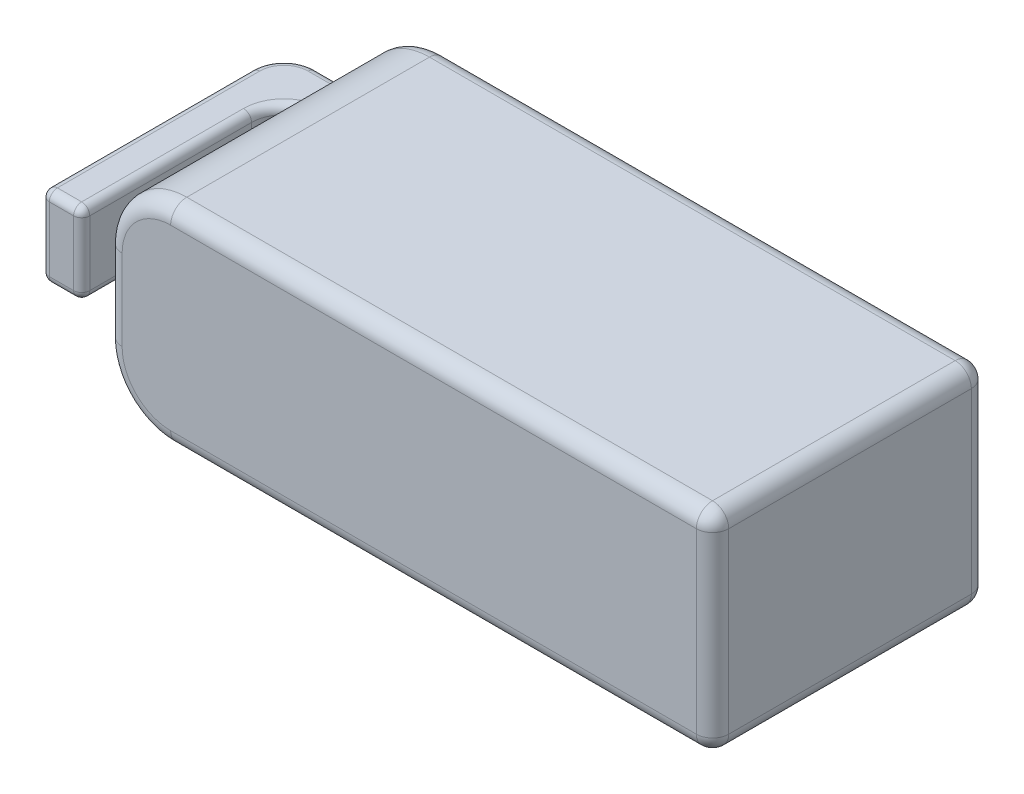
SolidWorks part; units mm, degrees
ref_plane "Plan de face" through (0, 0, 0) normal (0, 0, 1) x (1, 0, 0)
ref_plane "Plan de dessus" through (0, 0, 0) normal (0, 1, 0) x (1, 0, 0)
ref_plane "Plan de droite" through (0, 0, 0) normal (1, 0, 0) x (0, 0, -1)
sketch "Esquisse2" plane through (0, 0, 0) normal (0, 1, 0) x (1, 0, 0)
  line L2 (36.7424, -19.9217) -> (-38.2576, -19.9217)
  line L3 (36.7424, -19.9217) -> (36.7424, 14.0783)
  line L4 (36.7424, 14.0783) -> (-38.2576, 14.0783)
  line L5 (-38.2576, -19.9217) -> (-38.2576, 14.0783)
  line L6 (36.7424, -19.9217) -> (-38.2576, 14.0783) construction
  line L7 (36.7424, 14.0783) -> (-38.2576, -19.9217) construction
  point P1 (-0.7576, -2.9217)
  dimension "D1" = 75
  dimension "D2" = 34
extrude "Boss.-Extru.1" add sketch "Esquisse2" along normal blind 26
fillet "Congé1" radius 8 2 edges at (-38.2576, 0, 2.9217) (-38.2576, 26, 2.9217)
fillet "Congé2" radius 2 14 edges at (3.2424, 26, 19.9217) (-35.9144, 23.6569, 19.9217) (-38.2576, 13, 19.9217) (-35.9144, 2.3431, 19.9217) (3.2424, 26, -14.0783) (-35.9144, 23.6569, -14.0783) (-38.2576, 13, -14.0783) (-35.9144, 2.3431, -14.0783) (3.2424, 0, -14.0783) (36.7424, 13, 19.9217) (36.7424, 26, 2.9217) (36.7424, 13, -14.0783) (36.7424, 0, 2.9217) (3.2424, 0, 19.9217)
sketch "Esquisse3" plane through (-38.2576, 0, 0) normal (-1, 0, 0) x (0, 0, 1)
  line L4 (-12.0783, 8) -> (17.9217, 8)
  line L5 (17.9217, 8) -> (17.9217, 18)
  line L6 (17.9217, 18) -> (-12.0783, 18)
  line L7 (-12.0783, 18) -> (-12.0783, 8)
  line L8 (-12.0783, 8) -> (17.9217, 8)
  line L9 (17.9217, 8) -> (17.9217, 18)
  line L10 (17.9217, 18) -> (-12.0783, 18)
  line L11 (-12.0783, 18) -> (-12.0783, 8)
  dimension "D1" = 0
extrude "Boss.-Extru.2" add sketch "Esquisse3" along normal blind 10
sketch "Esquisse4" plane through (0, 18, 0) normal (0, 1, 0) x (1, 0, 0)
  line L0 (-38.2576, 7.0783) -> (-39.2576, 7.0783)
  line L1 (-43.2576, 3.0783) -> (-43.2576, -17.9217)
  line L4 (-38.2576, -17.9217) -> (-38.2576, 12.0783)
  line L5 (-38.2576, 12.0783) -> (-48.2576, 12.0783)
  line L6 (-48.2576, 12.0783) -> (-48.2576, -17.9217)
  line L7 (-48.2576, -17.9217) -> (-38.2576, -17.9217)
  line L8 (-38.2576, -17.9217) -> (-38.2576, 12.0783)
  line L9 (-38.2576, 12.0783) -> (-44.2576, 12.0783)
  line L10 (-48.2576, 8.0783) -> (-48.2576, -17.9217)
  line L11 (-48.2576, -17.9217) -> (-38.2576, -17.9217)
  arc A0 (-39.2576, 7.0783) -> (-43.2576, 3.0783) centre (-39.2576, 3.0783) ccw
  arc A1 (-44.2576, 12.0783) -> (-48.2576, 8.0783) centre (-44.2576, 8.0783) ccw
  point P6 (-43.2576, -7.4217)
  line M6 (-38.2576, -17.9217) -> (-38.2576, 12.0783)
  line M7 (-38.2576, 12.0783) -> (-48.2576, 12.0783)
  line M8 (-48.2576, 12.0783) -> (-48.2576, -17.9217)
  line M9 (-48.2576, -17.9217) -> (-38.2576, -17.9217)
  dimension "D4" = 4
  dimension "D2" = 5
  dimension "D3" = 5
  dimension "D1" = 0
extrude "Enlèv. mat.-Extru.1" cut sketch "Esquisse4" against normal blind 10 contours L0 A0 L1 M9 M6 | A1 M7 M8 region at (-40.7122, 18, 5.7495) region at (-47.3641, 18, -11.1848)
fillet "Congé4" radius 1 16 edges at (-38.7576, 8, -7.0783) (-43.2576, 8, 7.4217) (-41.2576, 8, -12.0783) (-47.086, 8, -10.9067) (-38.7576, 18, -7.0783) (-42.086, 18, -5.9067) (-41.2576, 18, -12.0783) (-47.086, 18, -10.9067) (-48.2576, 13, 17.9217) (-45.7576, 18, 17.9217) (-43.2576, 13, 17.9217) (-45.7576, 8, 17.9217) (-42.086, 8, -5.9067) (-48.2576, 8, 4.9217) (-43.2576, 18, 7.4217) (-48.2576, 18, 4.9217)
